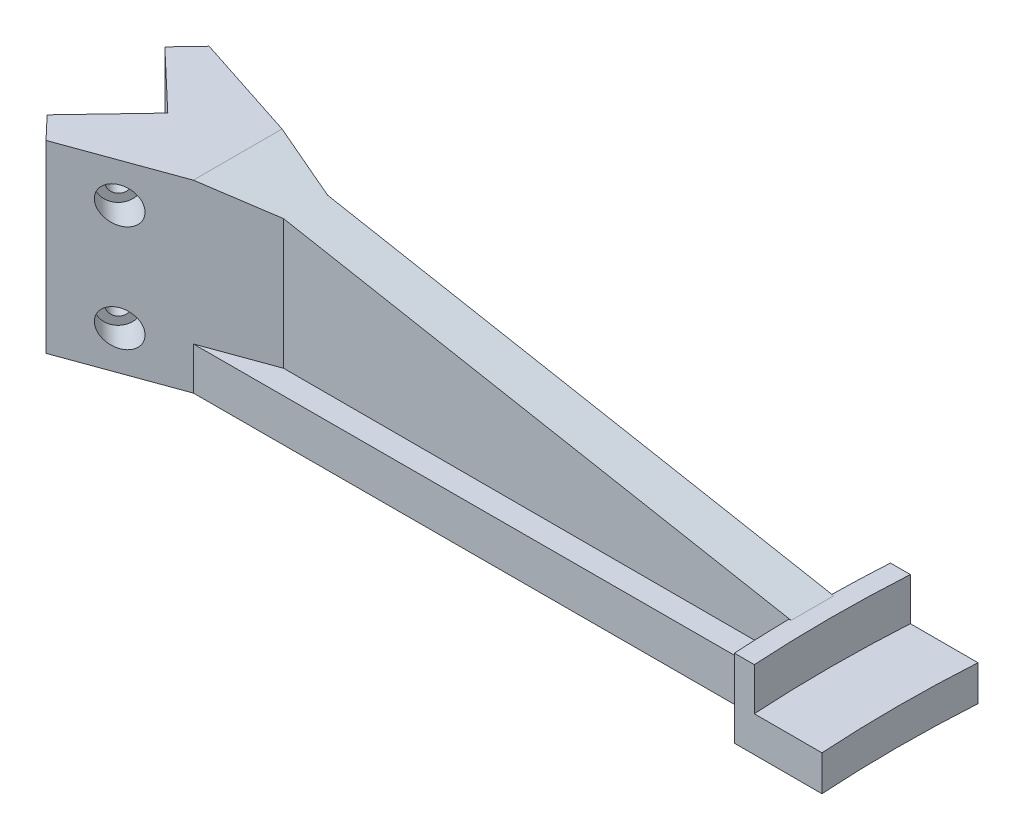
SolidWorks part; units mm, degrees
ref_plane "Front Plane" through (0, 0, 0) normal (0, 0, 1) x (1, 0, 0)
ref_plane "Top Plane" through (0, 0, 0) normal (0, 1, 0) x (1, 0, 0)
ref_plane "Right Plane" through (0, 0, 0) normal (1, 0, 0) x (0, 0, -1)
sketch "Sketch2" plane through (0, 0, 0) normal (0, 1, 0) x (1, 0, 0)
  line L0 (0, 0) -> (-181.1246, 0) construction
  line L1 (0, 0) -> (135.9511, 0) construction
  line L2 (-181.1246, 0) -> (-197.6966, 15.7434)
  line L3 (-197.6966, 15.7434) -> (-191.6108, 22.1496)
  line L4 (-191.6108, 22.1496) -> (-181.1246, 12.1877)
  line L5 (-181.1246, 12.1877) -> (-181.1246, 0)
  line L14 (0.6536, 22) -> (25.3402, 22)
  line L15 (0.6536, -22) -> (25.3402, -22)
  line L16 (25.3402, 22) -> (25.3402, -22) construction
  line L34 (-181.1246, 0) -> (-197.6966, -17.4443)
  line L49 (-197.6966, -17.4443) -> (-191.6108, -23.8504)
  line L50 (-191.6108, -23.8504) -> (-181.1246, -12.8123)
  line L51 (-181.1246, -12.8123) -> (-181.1246, 0)
  line L52 (-181.1246, 12.1877) -> (0.2109, 12.5)
  line L53 (-181.1246, -12.8123) -> (0.2109, -12.5)
  line L54 (0.2109, -12.5) -> (0.2109, 12.5) construction
  line L55 (-181.1246, 12.1877) -> (-181.1246, 24.2548) construction
  line L56 (-181.1246, -12.8123) -> (-181.1246, -19.1381)
  line L58 (-191.6108, 22.1496) -> (-161.1246, 12.2221)
  line L62 (-191.6108, -23.8504) -> (-161.1246, -12.7779)
  line L63 (-161.1246, 12.2221) -> (-161.1246, -12.7779)
  line L64 (-161.1246, -12.7779) -> (-124.8315, 0.4038)
  line L65 (-161.1246, 12.2221) -> (-124.8315, 0.4038)
  arc A0 (0.6536, 22) -> (0.6536, -22) centre (370.6, 0) ccw
  arc A1 (6.2636, 22) -> (6.2636, -22) centre (370.6, 0) ccw
  arc A2 (25.3402, 22) -> (25.3402, -22) centre (370.6, 0) ccw
  point P12 (-219.4633, -12.8783)
  point P25 (0, 0)
  point P27 (0, 0)
  point P28 (-148.6931, -34.0679)
  point P32 (5.6, 0)
  dimension "D2" = 365
  dimension "D3" = 5.6
  dimension "D4" = 19.04
  dimension "D7" = 25
  dimension "D5" = 133.531
  dimension "D6" = 136.469
  dimension "D8" = 25
  dimension "D9" = 44
  dimension "D10" = 20
  dimension "D18" = 46
  dimension "D19" = 186.7246
extrude "Boss-Extrude2" add sketch "Sketch2" against normal blind 12 contours A0 L52 L53 | L53 L52 | L53 | L52 | A1 L14 A0 L15 | L50 L51 L34 L49 | L5 L4 L3 L2 | L65 L63 L64 region at (-188.0032, 0, -12.1717) region at (-188.0032, 0, 13.1665) region at (-171.1246, 0, 0.2951) region at (-177.9533, 0, -15.5198) region at (-177.9533, 0, 16.4802) region at (-149.0269, 0, 0.0507) region at (-71.8375, 0, 0.1503) region at (3.0196, 0, 0)
extrude "Boss-Extrude3" add sketch "Sketch2<5>" along normal blind 10 from surface contours A2 L14 A1 L15 region at (15.3473, 0, 0) starting at face at (-97.5736, -12, 0.3044)
sketch "Sketch2<5>" plane through (0, 0, 0) normal (0, 1, 0) x (1, 0, 0) same geometry as "Sketch2"
extrude "Boss-Extrude4" add sketch "Sketch2<6>" along normal blind 22 from surface contours A1 L14 A0 L15 region at (3.0196, 0, 0) starting at face at (-94.6416, -12, 0.3044)
sketch "Sketch2<6>" plane through (0, 0, 0) normal (0, 1, 0) x (1, 0, 0) same geometry as "Sketch2"
extrude "Boss-Extrude7" add sketch "Sketch2<9>" along normal blind 40 contours L63 L52 L5 L51 L53 | L5 L4 L3 L2 | L58 L4 L52 | L50 L51 L34 L49 | L50 L62 L53 | L65 L63 L64 region at (-188.0032, 0, -12.1717) region at (-188.0032, 0, 13.1665) region at (-171.1246, 0, 0.2951) region at (-177.9533, 0, -15.5198) region at (-177.9533, 0, 16.4802) region at (-149.0269, 0, 0.0507)
sketch "Sketch2<9>" plane through (0, 0, 0) normal (0, 1, 0) x (1, 0, 0) same geometry as "Sketch2"
sketch "Sketch4" plane through (0, 0, 0) normal (0, 0, 1) x (1, 0, 0)
  line L2 (-197.6966, -12) -> (-197.6966, 40) construction
  line L5 (0.6536, 10) -> (-161.1246, 40)
  line L6 (-191.6108, 40) -> (-124.8315, 40) construction
  line L8 (-181.1246, 0) -> (0.2109, 0) construction
  line L9 (-161.1246, 0) -> (0.6536, 0)
  line L10 (0.6536, 0) -> (0.6536, 10)
  line L11 (0.6536, -12) -> (0.6536, 10) construction
  line L12 (0.6536, 10) -> (0, 10) construction
  line L13 (-161.1246, 40) -> (-161.1246, 0)
  dimension "D1" = 36.572
extrude "Boss-Extrude17" add sketch "Sketch4" along normal blind 6 and the other way blind 6
sketch "Sketch5" plane through (0, 0, 0) normal (0, 0, 1) x (1, 0, 0)
  line L0 (0.6536, 10) -> (-161.1246, 40) construction
  line L1 (0.6536, 10) -> (-161.1246, 40)
extrude "Cut-Extrude-Thin1" cut sketch "Sketch5" against normal through all and the other way through all thin contours L1 thin type one direction wall 10
sketch "Sketch6" plane through (-95.2035, 0, -90.4433) normal (-0.725, 0, -0.6887) x (-0.6887, 0, 0.725)
  line L0 (134.7494, 29) -> (134.7494, -1) construction
  line L1 (124.7494, 40) -> (148.8105, 40) construction
  line L2 (124.7494, 40) -> (144.7494, 40)
  line L3 (124.7494, 40) -> (124.7494, -12)
  line L4 (124.7494, -12) -> (144.7494, -12)
  line L5 (144.7494, 40) -> (144.7494, -12)
  line L6 (124.7494, 40) -> (144.7494, -12) construction
  line L7 (124.7494, -12) -> (144.7494, 40) construction
  line L8 (124.7494, -12) -> (124.7494, 40) construction
  line L9 (124.7494, -12) -> (148.8105, -12) construction
  circle A0 centre (134.7494, 29) radius 5
  circle A1 centre (134.7494, -1) radius 5
  circle A2 centre (134.7494, 29) radius 2.75
  circle A3 centre (134.7494, -1) radius 2.75
  point P3 (134.7494, 14)
  point P6 (134.7494, 14)
  dimension "D2" = 10
  dimension "D3" = 5.5
  dimension "D1" = 20
  dimension "D4" = 30
extrude "Cut-Extrude1" cut sketch "Sketch6" against normal through all from offset 8 contours A0 | A1 offset against normal yes
extrude "Cut-Extrude2" cut sketch "Sketch6<4>" against normal through all both and the other way through all contours A2 | A3
sketch "Sketch6<4>" plane through (-95.2035, 0, -90.4433) normal (-0.725, 0, -0.6887) x (-0.6887, 0, 0.725) same geometry as "Sketch6"
mirror "Mirror1" about plane through (0, 0, 0) normal (0, 0, 1) of "Cut-Extrude1", "Cut-Extrude2"
